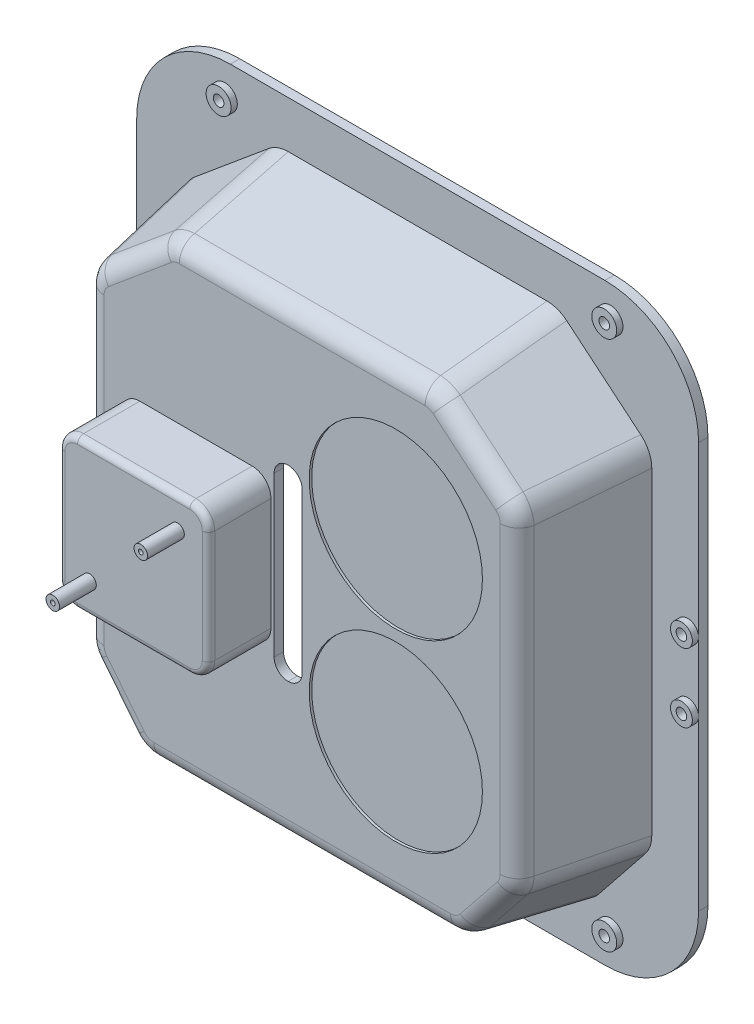
SolidWorks part; units mm, degrees
ref_plane "Front Plane" through (0, 0, 0) normal (0, 0, 1) x (1, 0, 0)
ref_plane "Top Plane" through (0, 0, 0) normal (0, 1, 0) x (1, 0, 0)
ref_plane "Right Plane" through (0, 0, 0) normal (1, 0, 0) x (0, 0, -1)
sketch "SK_Brim_180x190" plane through (0, 0, 0) normal (0, 0, 1) x (1, 0, 0)
  line L1 (-90, -95) -> (90, -95)
  line L2 (-90, -95) -> (-90, 95)
  line L3 (-90, 95) -> (90, 95)
  line L4 (90, -95) -> (90, 95)
  line L5 (-72, -77) -> (72, -77)
  line L6 (-72, -77) -> (-72, 77)
  line L7 (-72, 77) -> (72, 77)
  line L8 (72, -77) -> (72, 77)
extrude "Board_Mount_Brim_3mm" add sketch "SK_Brim_180x190" along normal blind 3
fillet "Brim_Outer_R30" radius 30 4 edges at (-90, 95, 1.5) (90, 95, 1.5) (90, -95, 1.5) (-90, -95, 1.5)
fillet "Brim_Inner_R10" radius 10 4 edges at (-72, 77, 1.5) (72, 77, 1.5) (72, -77, 1.5) (-72, -77, 1.5)
sketch "SK_Cockpit_Octagon" plane through (0, 0, 3) normal (0, 0, 1) x (1, 0, 0)
  line L0 (-55, -80) -> (55, -80)
  line L1 (55, -80) -> (75, -55)
  line L2 (75, -55) -> (75, 55)
  line L3 (75, 55) -> (45, 80)
  line L4 (45, 80) -> (-45, 80)
  line L5 (-45, 80) -> (-75, 55)
  line L6 (-75, 55) -> (-75, -55)
  line L7 (-75, -55) -> (-55, -80)
extrude "Cockpit_Canopy_37H_Draft10deg" add sketch "SK_Cockpit_Octagon" along normal blind 37 draft 10
fillet "Canopy_Corners_R10" radius 10 8 edges at (-71.738, -53.8557, 21.5) (-71.738, 53.4721, 21.5) (-43.819, 76.738, 21.5) (43.819, 76.738, 21.5) (71.738, 53.4721, 21.5) (71.738, -53.8557, 21.5) (53.4322, -76.738, 21.5) (-53.4322, -76.738, 21.5)
fillet "Canopy_Roof_R6" radius 6 16 edges at (-60.5695, -62.5944, 40) (0, -73.4759, 40) (60.5695, -62.5944, 40) (68.4759, -0.9626, 40) (55.1547, 63.0453, 40) (0, 73.4759, 40) (-55.1547, 63.0453, 40) (-68.4759, -0.9626, 40) (-51.398, -72.5055, 40) (51.398, -72.5055, 40) (67.9212, -52.5169, 40) (67.5476, 51.5095, 40) (42.4252, 72.8883, 40) (-42.4252, 72.8883, 40) (-67.5476, 51.5095, 40) (-67.9212, -52.5169, 40)
sketch "SK_Symmetric_Cavity" plane through (0, 0, 0) normal (0, 0, -1) x (-1, 0, 0)
  line L0 (-53, -77) -> (53, -77)
  line L1 (57.3444, -77) -> (-57.3444, -77) construction
  line L2 (53, -77) -> (72, -52)
  line L3 (72, 57.4649) -> (72, -58.75) construction
  line L4 (72, -52) -> (72, 52)
  line L5 (72, 52) -> (43, 77)
  line L6 (-62, 77) -> (62, 77) construction
  line L7 (43, 77) -> (-43, 77)
  line L8 (-43, 77) -> (-72, 52)
  line L9 (-72, -67) -> (-72, 67) construction
  line L10 (-72, 52) -> (-72, -52)
  line L11 (-72, -52) -> (-53, -77)
extrude "Symmetric_Electronics_Cavity_37H" cut sketch "SK_Symmetric_Cavity" against normal blind 37 draft 10
sketch "Sketch14" plane through (0, 0, 40) normal (0, 0, 1) x (1, 0, 0)
  line L1 (-58, -24) -> (-10, -24)
  line L2 (-58, -24) -> (-58, 24)
  line L3 (-58, 24) -> (-10, 24)
  line L4 (-10, -24) -> (-10, 24)
extrude "LD06_Raised_Base_20H" add sketch "Sketch14" along normal blind 20
fillet "Fillet3" radius 6 4 edges at (-58, 24, 50) (-10, 24, 50) (-10, -24, 50) (-58, -24, 50)
fillet "Fillet4" radius 2 8 edges at (-58, 0, 60) (-34, -24, 60) (-10, 0, 60) (-34, 24, 60) (-56.2426, -22.2426, 60) (-11.7574, -22.2426, 60) (-11.7574, 22.2426, 60) (-56.2426, 22.2426, 60)
sketch "Sketch15" plane through (0, 0, 60) normal (0, 0, 1) x (1, 0, 0)
  circle A0 centre (-48.1, -14.1) radius 2.15
  circle A1 centre (-19.9, 14.1) radius 2.15
extrude "Boss-Extrude6" add sketch "Sketch15" along normal blind 11.8
sketch "Sketch16" plane through (0, 0, 71.8) normal (0, 0, 1) x (1, 0, 0)
  circle A0 centre (-48.1, -14.1) radius 0.75
  circle A1 centre (-19.9, 14.1) radius 0.75
extrude "Cut-Extrude10" cut sketch "Sketch16" against normal blind 11.3
sketch "Sketch19" plane through (0, 0, 0) normal (0, 0, 1) x (1, 0, 0)
  line L0 (-50, -73) -> (50, -73)
  line L1 (-72, -77) -> (72, -77)
  line L2 (-72, -77) -> (-72, 77)
  line L3 (-72, 77) -> (72, 77)
  line L4 (72, -77) -> (72, 77)
  line L5 (50, -73) -> (68, -50)
  line L6 (68, -50) -> (68, 50)
  line L7 (68, 50) -> (40, 73)
  line L8 (40, 73) -> (-40, 73)
  line L9 (-40, 73) -> (-68, 50)
  line L10 (-68, 50) -> (-68, -50)
  line L11 (-68, -50) -> (-50, -73)
extrude "Boss-Extrude7" add sketch "Sketch19" along normal blind 3
sketch "Sketch20" plane through (0, 0, 3) normal (0, 0, 1) x (1, 0, 0)
  circle A0 centre (-86.5, -11) radius 1.7
  circle A1 centre (-86.5, 11) radius 1.7
  circle A2 centre (86.5, -11) radius 1.7
  circle A3 centre (86.5, 11) radius 1.7
  circle A4 centre (-61.7761, -84.9997) radius 1.7
  circle A5 centre (61.7761, -84.9997) radius 1.7
  circle A6 centre (-61.7761, 84.9997) radius 1.7
  circle A7 centre (61.7761, 84.9997) radius 1.7
extrude "Cut-Extrude13" cut sketch "Sketch20" against normal blind 3.2
sketch "Sketch21" plane through (0, 0, 40) normal (0, 0, 1) x (1, 0, 0)
  circle A0 centre (30, -29.5) radius 27.75
extrude "Cut-Extrude14" cut sketch "Sketch21" against normal blind 0.8
sketch "Sketch22" plane through (0, 0, 40) normal (0, 0, 1) x (1, 0, 0)
  circle A0 centre (30, 29.5) radius 27.75
extrude "Cut-Extrude15" cut sketch "Sketch22" against normal blind 0.8
sketch "Sketch24" plane through (0, 0, 40) normal (0, 0, 1) x (1, 0, 0)
  line L1 (-9, -30) -> (0, -30)
  line L2 (-9, -30) -> (-9, 30)
  line L3 (-9, 30) -> (0, 30)
  line L4 (0, -30) -> (0, 30)
extrude "Cut-Extrude18" cut sketch "Sketch24" against normal blind 4
fillet "Fillet5" radius 4.5 4 edges at (-9, -30, 38.5) (0, -30, 38.5) (0, 30, 38.5) (-9, 30, 38.5)
sketch "Sketch25" plane through (0, 0, 3) normal (0, 0, 1) x (1, 0, 0)
  circle A0 centre (-86.5, -11) radius 4
  circle A1 centre (-86.5, -11) radius 1.7
  circle A2 centre (-86.5, 11) radius 4
  circle A3 centre (-86.5, 11) radius 1.7
  circle A4 centre (86.5, -11) radius 3.5
  circle A5 centre (86.5, -11) radius 1.7
  circle A6 centre (86.5, 11) radius 3.5
  circle A7 centre (86.5, 11) radius 1.7
  circle A8 centre (-61.7761, -84.9997) radius 4
  circle A9 centre (-61.7761, -84.9997) radius 1.7
  circle A10 centre (61.7761, -84.9997) radius 4
  circle A11 centre (61.7761, -84.9997) radius 1.7
  circle A12 centre (-61.7761, 84.9997) radius 4
  circle A13 centre (-61.7761, 84.9997) radius 1.7
  circle A14 centre (61.7761, 84.9997) radius 4
  circle A15 centre (61.7761, 84.9997) radius 1.7
extrude "Boss-Extrude8" add sketch "Sketch25" along normal blind 2
sketch "SK_LD06_Hollow_Pedestal_Pockets" plane through (0, 0, 37) normal (0, 0, -1) x (-1, 0, 0)
  line L1 (28, 3) -> (52, 3)
  line L2 (28, 3) -> (28, 18)
  line L3 (28, 18) -> (52, 18)
  line L4 (52, 3) -> (52, 18)
  line L5 (16, -18) -> (40, -18)
  line L6 (16, -18) -> (16, -3)
  line L7 (16, -3) -> (40, -3)
  line L8 (40, -18) -> (40, -3)
extrude "LD06_Hollow_Pedestal_Pockets" cut sketch "SK_LD06_Hollow_Pedestal_Pockets" against normal blind 20
